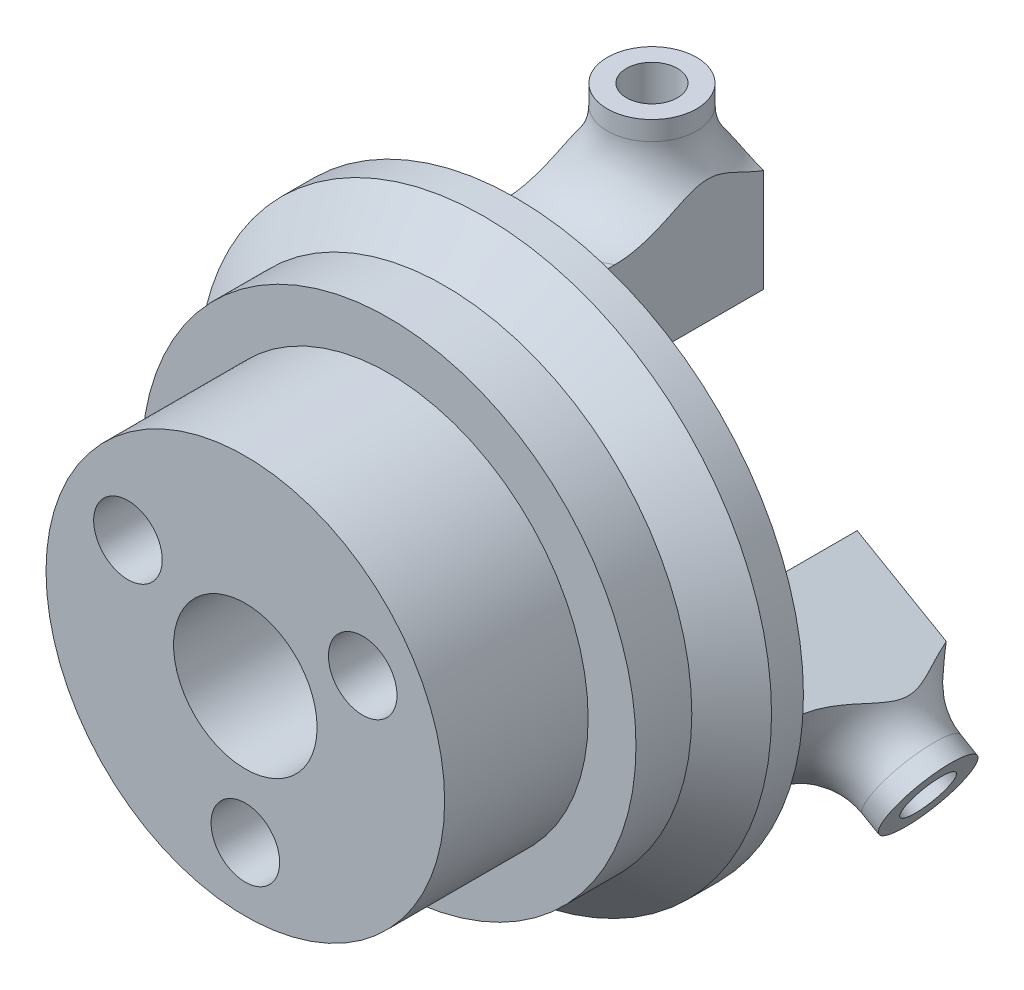
SolidWorks part; units mm, degrees
material "PE Low/Medium Density"
ref_plane "Front Plane" through (0, 0, 0) normal (0, 0, 1) x (1, 0, 0)
ref_plane "Top Plane" through (0, 0, 0) normal (0, 1, 0) x (1, 0, 0)
ref_plane "Right Plane" through (0, 0, 0) normal (1, 0, 0) x (0, 0, -1)
sketch "Sketch1" plane through (0, 0, 0) normal (0, 0, 1) x (1, 0, 0)
  circle A0 centre (0, 0) radius 18
  circle A1 centre (0, 0) radius 4
  dimension "D1" = 36
  dimension "D2" = 8
extrude "Boss-Extrude1" add sketch "Sketch1" along normal mid plane 5
sketch "Sketch5" plane through (0, 0, -2.5) normal (0, 0, 1) x (1, 0, 0)
  circle A0 centre (0, 0) radius 4
  circle A1 centre (0, 0) radius 4 construction
  circle A2 centre (0, 0) radius 7.5
  dimension "D1" = 15
extrude "Boss-Extrude3" add sketch "Sketch5" along normal blind 1
sketch "Sketch8" plane through (0, 0, 2.5) normal (0, 0, 1) x (1, 0, 0)
  circle A0 centre (0, 0) radius 4.5
  circle A1 centre (0, 0) radius 12.5
  dimension "D1" = 25
  dimension "D2" = 9
extrude "Boss-Extrude5" add sketch "Sketch8" along normal blind 12 contours A0 | A1
sketch "Sketch9" plane through (0, 0, 2.5) normal (0, 0, 1) x (1, 0, 0)
  circle A0 centre (0, 0) radius 12.5
  circle A1 centre (0, 0) radius 15.5
  circle A2 centre (0, 0) radius 12.5 construction
  dimension "D1" = 3
extrude "Boss-Extrude6" add sketch "Sketch9" along normal blind 3
hole_wizard "M4 Clearance Hole1" positions "Sketch12" profile "Sketch13" hole size "M4" standard "ANSI Metric" end condition through all
sketch "Sketch12" plane through (0, 0, 14.5) normal (0, 0, 1) x (1, 0, 0)
  line L2 (-7.3612, 4.25) -> (0, 0) construction
  line L3 (0, 0) -> (0, -8.5) construction
  line L4 (0, 8.5) -> (0, 12.5) construction
  line L6 (0, 8.5) -> (0, 4.5) construction
  line L7 (0, 0) -> (7.3612, 4.25) construction
  circle A0 centre (0, 0) radius 8.5 construction
  circle A4 centre (0, 0) radius 12.5 construction
  circle A5 centre (0, 0) radius 12.5 construction
  circle A6 centre (0, 0) radius 4.5 construction
  point P0 (7.3612, 4.25)
  point P2 (-7.3612, 4.25)
  point P4 (0, -8.5)
  dimension "D1" = 60
  dimension "D2" = 120
  dimension "D3" = 120
sketch "Sketch13" plane through (7.3612, 4.25, 14.5) normal (1, 0, 0) x (0, -1, 0)
  line L0 (0, 0) -> (0, 17)
  line L1 (0, 17) -> (2.15, 17)
  line L2 (2.15, 17) -> (2.15, 0)
  line L5 (2.15, 0) -> (0, 0)
  line L11 (0, -6.35) -> (0, 107.95) construction
  dimension "Thru Hole Dia." = 4.3
  dimension "Thru Hole Depth" = 17
sketch "Sketch14" plane through (0, 0, -2.5) normal (0, 0, -1) x (-1, 0, 0)
  line L0 (-11.6913, 4.25) -> (-9.5263, 8)
  line L1 (-9.5263, 8) -> (-5.1962, 8)
  line L2 (-5.1962, 8) -> (-3.0311, 4.25)
  line L3 (-3.0311, 4.25) -> (-5.1962, 0.5)
  line L4 (-5.1962, 0.5) -> (-9.5263, 0.5)
  line L5 (-9.5263, 0.5) -> (-11.6913, 4.25)
  circle A0 centre (-7.3612, 4.25) radius 3.75 construction
  dimension "D1" = 7.5
extrude "Cut-Extrude2" cut sketch "Sketch14" against normal blind 2
pattern_circular "CirPattern2" count 3 over 360 about axis through (0, 0, 2.5) along (0, 0, -1) of "Cut-Extrude2" reverse direction yes
sketch "Sketch15" plane through (0, 0, -2.5) normal (0, 0, -1) x (-1, 0, 0)
  line L0 (0, 0) -> (0, 11.8) construction
  line L1 (-3.5, 8.8) -> (3.5, 8.8)
  line L2 (-3.5, 8.8) -> (-3.5, 14.8)
  line L3 (-3.5, 14.8) -> (3.5, 14.8)
  line L4 (3.5, 8.8) -> (3.5, 14.8)
  line L5 (-3.5, 8.8) -> (3.5, 14.8) construction
  line L6 (-3.5, 14.8) -> (3.5, 8.8) construction
  point P0 (0, 11.8)
  dimension "D1" = 14.8
  dimension "D2" = 6
  dimension "D3" = 7
extrude "Boss-Extrude7" add sketch "Sketch15" along normal blind 12
sketch "Sketch16" plane through (0, 14.8, 0) normal (0, 1, 0) x (1, 0, 0)
  line L0 (0, 11) -> (0, 0) construction
  circle A0 centre (0, 11) radius 2.8
  dimension "D1" = 5.6
  dimension "D2" = 11
extrude "Boss-Extrude8" add sketch "Sketch16" along normal blind 5.2
sketch "Sketch17" plane through (0, 20, 0) normal (0, 1, 0) x (1, 0, 0)
  circle A0 centre (0, 11) radius 1.6
  circle A1 centre (0, 11) radius 2.8 construction
  dimension "D1" = 3.2
extrude "Cut-Extrude3" cut sketch "Sketch17" against normal blind 9
ref_plane "Plane1" through (0, 18.55, 0) normal (0, 1, 0) x (1, 0, 0)
chamfer "Chamfer1" distance 3 angle 45 1 edges at (18, 0, 2.5)
sketch "Sketch18" plane through (0, 8.8, 0) normal (0, -1, 0) x (1, 0, 0)
  line L0 (-2.85, -9.3546) -> (0, -7.7091)
  line L1 (0, -7.7091) -> (2.85, -9.3546)
  line L2 (2.85, -9.3546) -> (2.85, -12.6454)
  line L3 (2.85, -12.6454) -> (0, -14.2909)
  line L4 (0, -14.2909) -> (-2.85, -12.6454)
  line L5 (-2.85, -12.6454) -> (-2.85, -9.3546)
  circle A0 centre (0, -11) radius 2.85 construction
  dimension "D1" = 5.7
extrude "Cut-Extrude5" cut sketch "Sketch18" against normal blind 2.85
fillet "Fillet3" radius 4 1 edges at (0, 14.8, -13.8)
fillet "Fillet5" radius 1 3 edges at (0, 8.8, -2.5) (3.5, 11.8, -2.5) (-3.5, 11.8, -2.5)
pattern_circular "CirPattern4" count 3 over 360 about axis through (0, 0, 2.5) along (0, 0, -1) of "Boss-Extrude7", "Boss-Extrude8", "Cut-Extrude3", "Cut-Extrude5", "Fillet3", "Fillet5"
